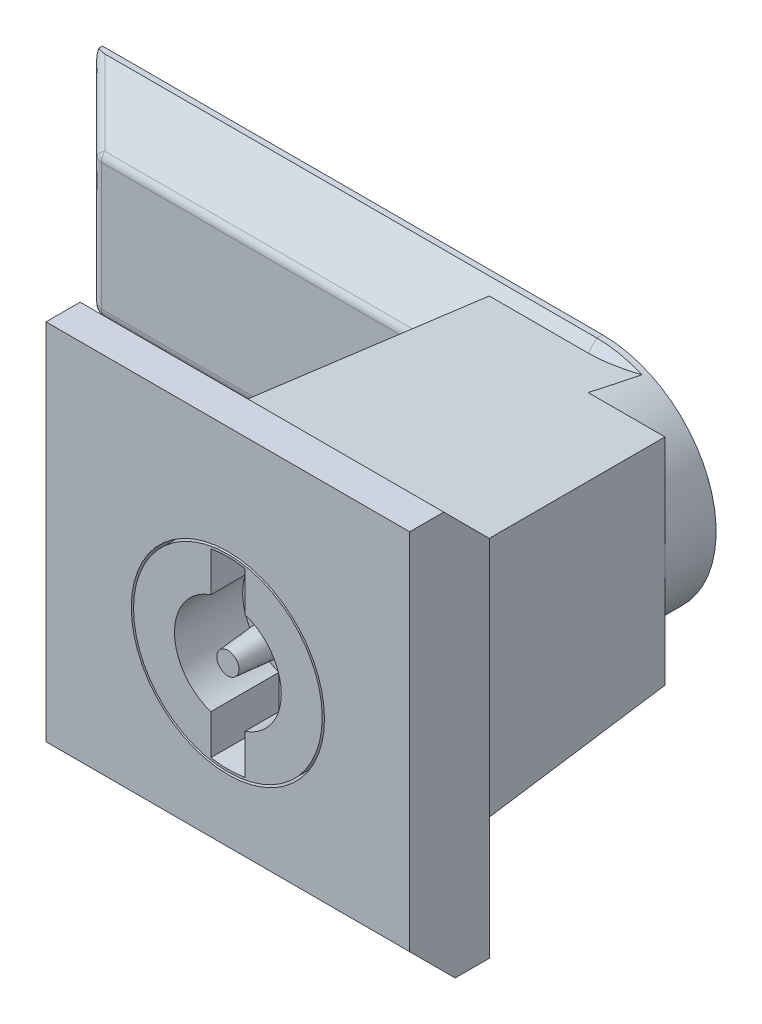
SolidWorks part; units mm, degrees
ref_plane "前视基准面" through (0, 0, 0) normal (0, 0, 1) x (1, 0, 0)
ref_plane "上视基准面" through (0, 0, 0) normal (0, 1, 0) x (1, 0, 0)
ref_plane "右视基准面" through (0, 0, 0) normal (1, 0, 0) x (0, 0, -1)
sketch "草图2" plane through (0, 0, 0) normal (0, 0, 1) x (1, 0, 0)
  line L1 (-16, 18) -> (16, 18)
  line L2 (-16, 18) -> (-16, -18)
  line L3 (-16, -18) -> (16, -18)
  line L4 (16, 18) -> (16, -18)
  line L5 (-16, 18) -> (16, -18) construction
  line L6 (-16, -18) -> (16, 18) construction
  point P0 (0, 0)
  dimension "D1" = 32
  dimension "D2" = 36
extrude "凸台-拉伸1" add sketch "草图2" against normal blind 7
chamfer "倒角1" distance 4 angle 45 2 edges at (0, 18, -7) (0, -18, 0)
sketch "草图3" plane through (0, 0, -7) normal (0, 0, -1) x (-1, 0, 0)
  line L4 (11, 9) -> (-11, 9)
  line L5 (-11, 9) -> (-11, -13)
  line L6 (-11, -13) -> (11, -13)
  line L7 (11, -13) -> (11, 9)
  line L8 (-14, -16) -> (14, -16)
  line L9 (14, -16) -> (14, 12)
  line L10 (14, 12) -> (-14, 12)
  line L11 (-14, 12) -> (-14, -16)
  line L12 (-14, -16) -> (14, -16)
  line L13 (14, -16) -> (14, 12)
  line L14 (14, 12) -> (-14, 12)
  line L15 (-14, 12) -> (-14, -16)
  dimension "D1" = 2
  dimension "D2" = 3
extrude "凸台-拉伸2" add sketch "草图3" along normal blind 2
sketch "草图4" plane through (0, 0, -7) normal (0, 0, -1) x (-1, 0, 0)
  line L0 (11, 9) -> (-11, 9) construction
  line L1 (-11, 9) -> (-11, -13) construction
  line L2 (-11, -13) -> (11, -13) construction
  line L3 (11, 9) -> (-11, 9)
  line L4 (-11, 9) -> (-11, -13)
  line L5 (-11, -13) -> (11, -13)
  line L6 (11, -13) -> (11, 9) construction
  line L7 (11, -13) -> (11, 9)
extrude "凸台-拉伸3" add sketch "草图4" along normal blind 22 draft 4
sketch "草图5" plane through (0, 0, -29) normal (0, 0, -1) x (-1, 0, 0)
  line L0 (9.4616, -2) -> (-9.4616, -2) construction
  line L1 (0.5384, 8) -> (44.5384, 8)
  line L2 (0.5384, 8) -> (0.5384, -12) construction
  line L3 (0.5384, -12) -> (44.5384, -12)
  line L4 (44.5384, 8) -> (44.5384, -12)
  line L5 (0.5384, 8) -> (44.5384, -12) construction
  line L6 (0.5384, -12) -> (44.5384, 8) construction
  line L7 (9.4616, -11.4616) -> (9.4616, 7.4616) construction
  line L8 (-9.4616, 7.4616) -> (-9.4616, -11.4616) construction
  arc A0 (0.5384, -12) -> (0.5384, 8) centre (0.5384, -2) cw
  point P0 (22.5384, -2)
  dimension "D1" = 20
  dimension "D2" = 44
extrude "凸台-拉伸4" add sketch "草图5" along normal blind 4.5
chamfer "倒角2" distance 4 angle 45 5 edges at (1.1023, -11.8645, -29) (1.1023, 7.8645, -29) (-22.5384, -12, -29) (-44.5384, -2, -29) (-22.5384, 8, -29)
sketch "草图6" plane through (0, 0, 0) normal (0, 0, 1) x (1, 0, 0)
  circle A0 centre (0, 0) radius 8.5
  circle A1 centre (0, 0) radius 8.3
  dimension "D1" = 17
  dimension "D2" = 0.2
extrude "切除-拉伸1" cut sketch "草图6" against normal blind 6
sketch "草图8" plane through (0, 0, 0) normal (0, 0, 1) x (1, 0, 0)
  line L0 (-8.1, 0) -> (8.1, 0) construction
  line L1 (0, 8.1) -> (0, -8.1) construction
  line L2 (-1.5, 4.4542) -> (-1.5, 7.9599)
  line L3 (1.5, 4.4542) -> (1.5, 7.9599)
  line L4 (1.5, -4.4542) -> (1.5, -7.9599)
  line L5 (-1.5, -4.4542) -> (-1.5, -7.9599)
  arc A1 (-1.5, 4.4542) -> (-1.5, -4.4542) centre (0, 0) ccw
  circle A2 centre (0, 0) radius 8.1
  circle A3 centre (0, 0) radius 8.1
  arc A4 (1.5, -4.4542) -> (1.5, 4.4542) centre (0, 0) ccw
  dimension "D2" = 9.4
  dimension "D3" = 1.5
  dimension "D1" = 0.2
extrude "切除-拉伸2" cut sketch "草图8" against normal blind 6 contours L4 A4 L3 A3 L2 A1 L5 region at (0, 0, 0)
sketch "草图9" plane through (0, 0, -6) normal (0, 0, 1) x (1, 0, 0)
  circle A0 centre (0, 0) radius 1.5
  dimension "D1" = 3
extrude "凸台-拉伸5" add sketch "草图9" along normal blind 6 draft 5
fillet "圆角1" radius 1 5 edges at (-42.5384, 6, -31) (-42.5384, -10, -31) (-25, -8, -29) (-40.5384, -2, -29) (-25, 4, -29)
